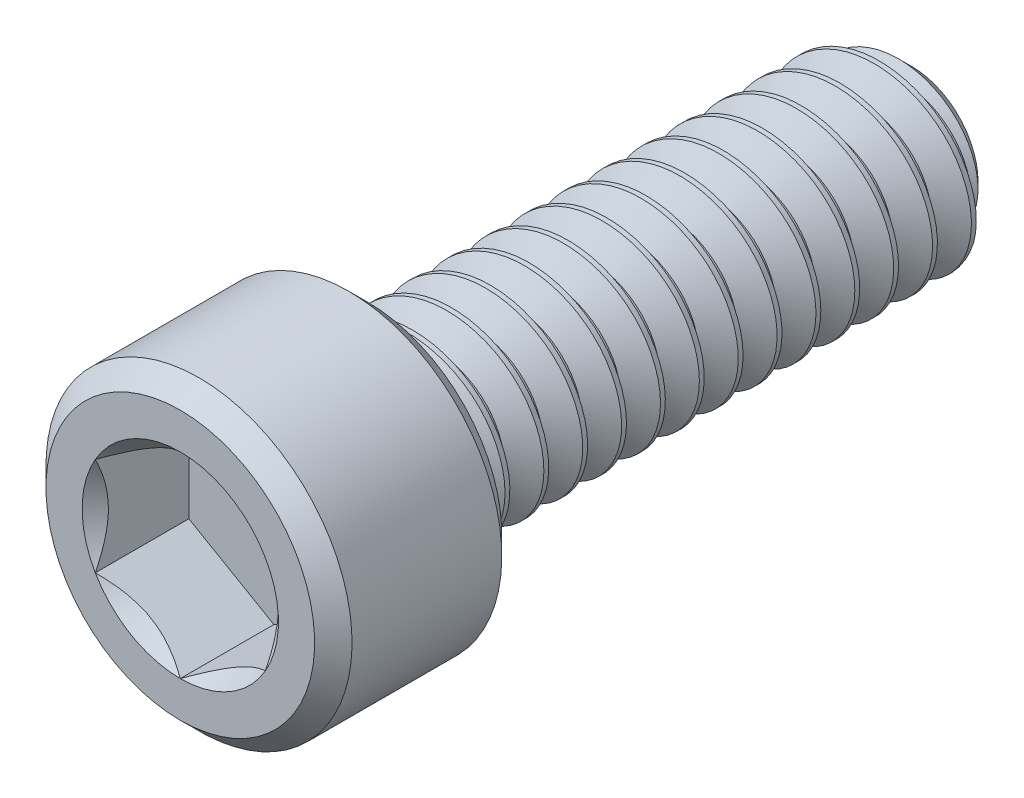
SolidWorks part; units mm, degrees
ref_plane "Front Plane" through (0, 0, 0) normal (0, 0, 1) x (1, 0, 0)
ref_plane "Top Plane" through (0, 0, 0) normal (0, 1, 0) x (1, 0, 0)
ref_plane "Right Plane" through (0, 0, 0) normal (1, 0, 0) x (0, 0, -1)
sketch "Sketch1" plane through (0, 0, 0) normal (1, 0, 0) x (0, 0, -1)
  line L0 (4.2672, 0) -> (-4.2672, 0) construction
  line L1 (-4.2672, 0) -> (-4.2672, 1.5675)
  line L2 (-4.2672, 1.5675) -> (-4.0488, 1.7859)
  line L3 (-4.0488, 1.7859) -> (-2.3012, 1.7859)
  line L4 (-2.3012, 1.7859) -> (-2.0828, 1.5675)
  line L5 (-2.0828, 1.5675) -> (-2.0828, 1.0922)
  line L6 (-2.0828, 1.0922) -> (3.9497, 1.0922)
  line L7 (3.9497, 1.0922) -> (4.2672, 0.7747)
  line L8 (4.2672, 0.7747) -> (4.2672, 0)
  line L9 (4.2389, 1.1413) -> (4.6924, 1.1413) construction
  line L10 (4.6924, 1.1413) -> (4.4656, 0.7485) construction
  line L11 (4.4656, 0.7485) -> (4.2389, 1.1413) construction
  line L12 (4.2672, 1.0922) -> (4.6641, 1.0922) construction
  line L13 (4.4656, 1.1413) -> (4.4656, 1.0922) construction
  line L14 (4.4373, 0.7976) -> (4.494, 0.7976) construction
  line L15 (4.4656, 0.7976) -> (4.4656, 0.7485) construction
  line L16 (4.253, 1.1168) -> (4.6782, 1.1168)
  line L17 (4.6782, 1.1168) -> (4.494, 0.7976)
  line L18 (4.494, 0.7976) -> (4.4373, 0.7976)
  line L19 (4.4373, 0.7976) -> (4.253, 1.1168)
  line L20 (3.9497, -1.0922) -> (3.1333, -1.0922) construction
  point P3 (-3.9395, 1.7859)
  point P4 (0, 0)
  point P25 (4.4656, 1.1168)
  point P26 (4.2672, 1.0922)
  point P28 (-2.4105, 1.7859)
  point P29 (-3.175, 1.7859)
  point P33 (3.1333, -1.0922)
  dimension "Head Ht" = 2.1844
  dimension "Screw Size" = 2.1844
  dimension "Head Dia" = 3.5719
  dimension "D1" = 45
  dimension "D2" = 45
  dimension "D3" = 0.2184
  dimension "D4" = 0.2184
  dimension "Pitch" = 0.4536
  dimension "D5" = 0.0567
  dimension "D6" = 0.3175
  dimension "D7" = 0.8164
  dimension "Length" = 6.35
  dimension "D8" = 0.1092
  dimension "D9" = 0.1092
sketch "Sketch2" plane through (0, 0, 0) normal (0, 0, 1) x (1, 0, 0)
  line L1 (0, 1.1457) -> (-0.9922, 0.5728)
  line L2 (-0.9922, 0.5728) -> (-0.9922, -0.5728)
  line L3 (-0.9922, -0.5728) -> (0, -1.1457)
  line L4 (0, -1.1457) -> (0.9922, -0.5728)
  line L5 (0.9922, -0.5728) -> (0.9922, 0.5728)
  line L6 (0.9922, 0.5728) -> (0, 1.1457)
  line L8 (0, -1.7859) -> (0, 1.7859) construction
  circle A0 centre (0, 0) radius 0.9922 construction
  circle A1 centre (0, 0) radius 1.7859
  circle A2 centre (0, 0) radius 18.0975 construction
  point P1 (0, 1.7859)
  point P19 (0, 0)
  dimension "D1" = 3.5719
  dimension "D3" = 36.195
  dimension "Drive Size" = 1.9844
sketch "Sketch3" plane through (0, 0, 0) normal (1, 0, 0) x (0, 0, -1)
  line L0 (4.2672, 0) -> (-4.2672, 0) construction
  line L1 (-4.2672, 0) -> (-4.2672, 1.5675) construction
  line L2 (-4.2672, 1.5675) -> (-4.0488, 1.7859) construction
  line L3 (-4.0488, 1.7859) -> (-2.3012, 1.7859) construction
  line L4 (-2.3012, 1.7859) -> (-2.0828, 1.5675) construction
  line L5 (-2.0828, 1.5675) -> (-2.0828, 1.0922) construction
  line L6 (-2.0828, 1.0922) -> (3.9497, 1.0922) construction
  line L7 (3.9497, 1.0922) -> (4.2672, 0.7747) construction
  line L8 (4.2672, 0.7747) -> (4.2672, 0) construction
  line L9 (4.2672, 0) -> (-4.2672, 0)
  line L10 (-4.2672, 0) -> (-4.2672, 1.5675)
  line L11 (-4.2672, 1.5675) -> (-4.0488, 1.7859)
  line L12 (-4.0488, 1.7859) -> (-2.3012, 1.7859)
  line L13 (-2.3012, 1.7859) -> (-2.0828, 1.5675)
  line L14 (-2.0828, 1.5675) -> (-2.0828, 1.0922)
  line L15 (-2.0828, 1.0922) -> (3.9497, 1.0922)
  line L16 (3.9497, 1.0922) -> (4.2672, 0.7747)
  line L17 (4.2672, 0.7747) -> (4.2672, 0)
revolve "Revolve1" add sketch "Sketch3" angle 360 about L0
sketch "Sketch4" plane through (0, 0, 4.2672) normal (0, 0, 1) x (1, 0, 0)
  line L0 (0, -1.1457) -> (0.9922, -0.5728) construction
  line L1 (0.9922, -0.5728) -> (0.9922, 0.5728) construction
  line L2 (0.9922, 0.5728) -> (0, 1.1457) construction
  line L3 (0, 1.1457) -> (-0.9922, 0.5728) construction
  line L4 (-0.9922, 0.5728) -> (-0.9922, -0.5728) construction
  line L5 (-0.9922, -0.5728) -> (0, -1.1457) construction
  line L6 (0, -1.1457) -> (0.9922, -0.5728)
  line L7 (0.9922, -0.5728) -> (0.9922, 0.5728)
  line L8 (0.9922, 0.5728) -> (0, 1.1457)
  line L9 (0, 1.1457) -> (-0.9922, 0.5728)
  line L10 (-0.9922, 0.5728) -> (-0.9922, -0.5728)
  line L11 (-0.9922, -0.5728) -> (0, -1.1457)
extrude "Cut-Extrude1" cut sketch "Sketch4" against normal blind 1.0922
sketch "Sketch5" plane through (0, 0, 4.2672) normal (0, 0, 1) x (1, 0, 0)
  circle A0 centre (0, 0) radius 1.1457
extrude "Cut-Extrude3" cut sketch "Sketch5" against normal through all draft 45
ref_axis "Center Axis1" through (0, 0, 2.0828) along (0, 0, -1)
split "Split1" bodies to split 107 resulting bodies 108 109 split by face at (0, 1.5675, 2.0828)
sketch "Sketch6" plane through (0, 0, -4.2672) normal (0, 0, -1) x (-1, 0, 0)
  circle A0 centre (0, 0) radius 1.0922 construction
  circle A1 centre (0, 0) radius 1.0922
curve "Helix/Spiral1" pitch 0.4536 height 6.8036 radius 1.0922 centre (0, 0, -4.2672) axis (0, 0, 1) start towards (0, 1, 0)
sketch "Sketch7" plane through (0, 0, 0) normal (1, 0, 0) x (0, 0, -1)
  line L0 (4.253, 1.1168) -> (4.6782, 1.1168) construction
  line L1 (4.6782, 1.1168) -> (4.494, 0.7976) construction
  line L2 (4.494, 0.7976) -> (4.4373, 0.7976) construction
  line L3 (4.4373, 0.7976) -> (4.253, 1.1168) construction
  line L4 (4.253, 1.1168) -> (4.6782, 1.1168)
  line L5 (4.6782, 1.1168) -> (4.494, 0.7976)
  line L6 (4.494, 0.7976) -> (4.4373, 0.7976)
  line L7 (4.4373, 0.7976) -> (4.253, 1.1168)
sweep "Cut-Sweep1" cut profiles "Sketch7" path "Helix/Spiral1" align with end faces yes
sketch "Sketch8" plane through (0, 0, 2.0828) normal (0, 0, -1) x (-1, 0, 0)
  circle A0 centre (0, 0) radius 1.0922
  point P3 (0, 1.0922)
extrude "Boss-Extrude1" add sketch "Sketch8" along normal blind 2.54 draft 80
equation "\"D3@Sketch1\"=\"Head Ht@Sketch1\"/10"
equation "\"D4@Sketch1\"=\"Head Ht@Sketch1\"/10"
equation "\"D5@Sketch1\"=\"Pitch@Sketch1\"/8"
equation "\"D6@Sketch1\"=\"Pitch@Sketch1\"*.7"
equation "\"D7@Sketch1\"=\"Pitch@Sketch1\"*2.5-\"D6@Sketch1\""
equation "\"D1@Cut-Extrude1\"=\"Head Ht@Sketch1\"/2"
equation "\"D4@Helix/Spiral1\"=\"Pitch@Sketch1\""
equation "\"D3@Helix/Spiral1\"=\"Length@Sketch1\"+\"D4@Helix/Spiral1\""
equation "\"D8@Sketch1\"=\"D4@Sketch1\"/2"
equation "\"D9@Sketch1\"=\"D3@Sketch1\"/2"
